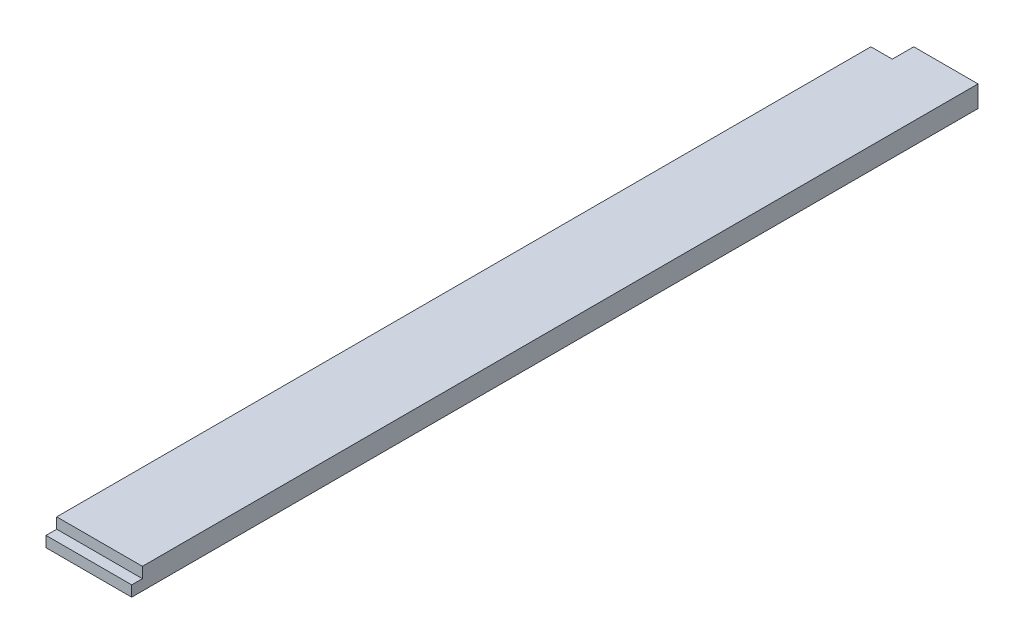
SolidWorks part; units mm, degrees
ref_plane "Front Plane" through (0, 0, 0) normal (0, 0, 1) x (1, 0, 0)
ref_plane "Top Plane" through (0, 0, 0) normal (0, 1, 0) x (1, 0, 0)
ref_plane "Right Plane" through (0, 0, 0) normal (1, 0, 0) x (0, 0, -1)
sketch "Sketch1" plane through (0, 0, 0) normal (0, 0, 1) x (1, 0, 0)
  line L0 (0, 12.7) -> (0, 6.35)
  line L3 (12.7, 0) -> (50.8, 0)
  line L4 (50.8, 0) -> (50.8, 12.7)
  line L5 (50.8, 12.7) -> (0, 12.7)
  line L6 (12.7, 0) -> (0, 0)
  line L7 (0, 0) -> (0, 6.35)
  dimension "D1" = 6.35
  dimension "D4" = 50.8
extrude "Boss-Extrude1" add sketch "Sketch1" along normal blind 501.65
sketch "Sketch2" plane through (0, 12.7, 0) normal (0, -1, 0) x (1, 0, 0)
  line L5 (50.8, 501.65) -> (50.8, 0) construction
  line L7 (50.8, 495.3) -> (0, 495.3)
  line L8 (50.8, 495.3) -> (50.8, 501.65)
  line L9 (50.8, 501.65) -> (0, 501.65)
  line L10 (0, 495.3) -> (0, 501.65)
  dimension "D1" = 6.35
extrude "Cut-Extrude1" cut sketch "Sketch2" along normal blind 6.35
sketch "Sketch3" plane through (0, 12.7, 0) normal (0, 1, 0) x (1, 0, 0)
  line L1 (0, 0) -> (12.7, 0)
  line L2 (0, 0) -> (0, -12.7)
  line L3 (0, -12.7) -> (12.7, -12.7)
  line L4 (12.7, 0) -> (12.7, -12.7)
  dimension "D1" = 12.7
  dimension "D2" = 12.7
extrude "Cut-Extrude2" cut sketch "Sketch3" against normal through all
